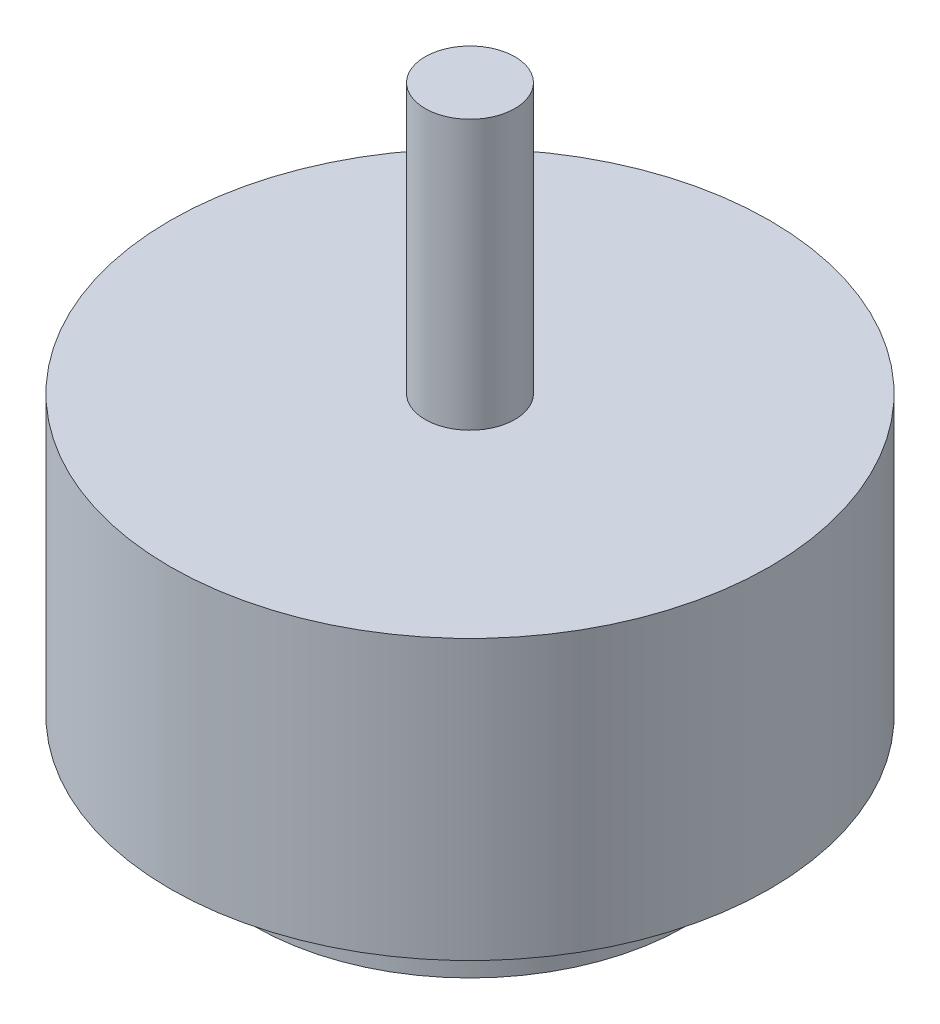
SolidWorks part; units mm, degrees
ref_plane "Front Plane" through (0, 0, 0) normal (0, 0, 1) x (1, 0, 0)
ref_plane "Top Plane" through (0, 0, 0) normal (0, 1, 0) x (1, 0, 0)
ref_plane "Right Plane" through (0, 0, 0) normal (1, 0, 0) x (0, 0, -1)
sketch "Sketch3" plane through (0, 0, 0) normal (0, 0, 1) x (1, 0, 0)
  line L0 (0, 0) -> (12, 0)
  line L1 (12, 0) -> (12, 2)
  line L2 (12, 2) -> (4.8649, 2)
  line L3 (4.8649, 2) -> (4.8649, 4.1622)
  line L4 (4.8649, 4.1622) -> (16.7, 4.1622)
  line L5 (16.7, 4.1622) -> (16.7, 19.7)
  line L6 (16.7, 19.7) -> (0, 19.7)
  line L7 (0, 19.7) -> (0, 0)
  dimension "D1" = 2
  dimension "D2" = 12
  dimension "D3" = 19.7
  dimension "D4" = 16.7
revolve "Revolve1" add sketch "Sketch3" angle 360 about L7
sketch "Sketch4" plane through (0, 19.7, 0) normal (0, 1, 0) x (1, 0, 0)
  circle A0 centre (0, 0) radius 2.5
  dimension "D1" = 5
extrude "Boss-Extrude1" add sketch "Sketch4" along normal offset from surface (15 mm away) 34.7 up to face at (-12, 0, 0)
sketch "Sketch5" plane through (0, 0, 0) normal (0, -1, 0) x (1, 0, 0)
  circle A0 centre (9.5, 0) radius 1.5
  circle A1 centre (0, -9.5) radius 1.5
  circle A2 centre (-9.5, 0) radius 1.5
  circle A3 centre (0, 9.5) radius 1.5
  dimension "D1" = 3
  dimension "D2" = 9.5
  dimension "D3" = 4
extrude "Cut-Extrude3" cut sketch "Sketch5" against normal blind 4
